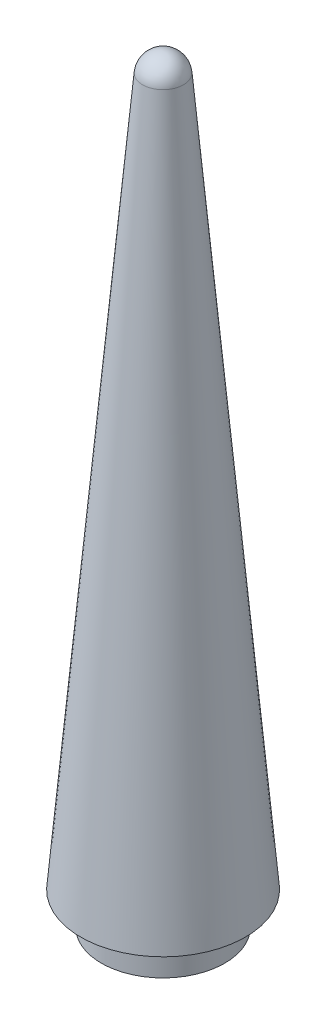
SolidWorks part; units mm, degrees
material "6061 Alloy"
ref_plane "Front Plane" through (0, 0, 0) normal (0, 0, 1) x (1, 0, 0)
ref_plane "Top Plane" through (0, 0, 0) normal (0, 1, 0) x (1, 0, 0)
ref_plane "Right Plane" through (0, 0, 0) normal (1, 0, 0) x (0, 0, -1)
sketch "Sketch2" plane through (0, 0, 0) normal (0, 0, 1) x (1, 0, 0)
  line L0 (0, -3.7271) -> (0, 141.5732)
  line L1 (0, 141.5732) -> (12.7121, -3.7271)
  line L2 (12.7121, -3.7271) -> (9.525, -3.7271)
  line L3 (9.525, -3.7271) -> (9.525, -8.8071)
  line L4 (9.525, -8.8071) -> (0, -8.8071)
  line L5 (0, -8.8071) -> (0, -3.7271)
  line L6 (0, 108.3192) -> (-2.1023, 108.3192) construction
  line L7 (0, -200166.8953) -> (0, 200141.5732) construction
  line L8 (12.7121, -3.7271) -> (-12.7121, -3.7271) construction
  line L9 (0, 141.5732) -> (26.9875, -166.8953) construction
  arc A0 (3.1629, 105.4209) -> (0, 108.3192) centre (0, 105.1442) ccw
  point P10 (0, 141.5732)
  point P12 (0, 109.1297)
  point P16 (3.1629, 105.4209)
  point P18 (5.7295, 0)
  point P19 (0, 0)
  point P20 (0, 0)
  point P21 (0, -3.7271)
  point P23 (0, 0)
  point P24 (12.7121, -3.7271)
  point P29 (8.4632, -2.4813)
  point P30 (8.7577, -2.5677)
  point P31 (9.525, -8.8071)
  point P33 (9.525, -2.7919)
  point P34 (9.5225, -8.8071)
  point P35 (0, 0)
revolve "Revolve1" add sketch "Sketch2" angle 360 about L0 region at (4.4401, 37.9904, 0)
sketch "Sketch3" plane through (0, -8.8071, 0) normal (0, -1, 0) x (1, 0, 0)
  point P0 (0, 0)
hole_wizard "1/4-20 Tapped Hole1" positions "Sketch3" profile "Sketch4" tap size "1/4-20" standard "ANSI Inch"
sketch "Sketch4" plane through (0, -8.8071, 0) normal (1, 0, 0) x (0, 0, -1)
  line L0 (0, 0) -> (0, 65.0338)
  line L1 (0, 65.0338) -> (2.5527, 63.5)
  line L2 (2.5527, 63.5) -> (2.5527, 1.2573)
  line L3 (2.5527, 1.2573) -> (3.81, 0)
  line L5 (3.81, 0) -> (0, 0)
  line L6 (-2.5527, 1.2573) -> (-3.81, 0) construction
  line L10 (0, 65.0338) -> (-2.5527, 63.5) construction
  line L11 (0, -6.35) -> (0, 107.95) construction
  dimension "Tap Drill Dia." = 5.1054
  dimension "Tap Drill Depth" = 63.5
  dimension "Near C'Sink Dia." = 7.62
  dimension "Near C'Sink Angle" = 90
  dimension "Drill Angle" = 118
cosmetic thread "Hole Thread1" parameters "D1"=50.8, "D2"=6.35
